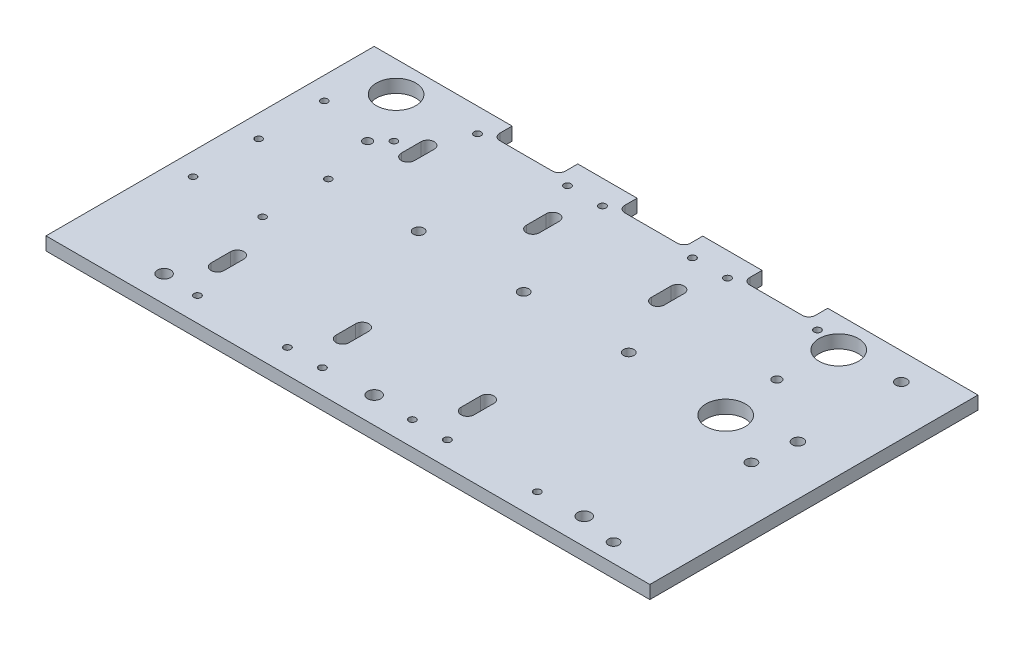
SolidWorks part; units mm, degrees
ref_plane "Front Plane" through (0, 0, 0) normal (0, 0, 1) x (1, 0, 0)
ref_plane "Top Plane" through (0, 0, 0) normal (0, 1, 0) x (1, 0, 0)
ref_plane "Right Plane" through (0, 0, 0) normal (1, 0, 0) x (0, 0, -1)
sketch "Sketch1" plane through (0, 0, 0) normal (0, 1, 0) x (1, 0, 0)
  line L1 (0, 0) -> (292.1, 0)
  line L2 (0, 0) -> (0, 158.75)
  line L3 (0, 158.75) -> (292.1, 158.75)
  line L4 (292.1, 0) -> (292.1, 158.75)
  dimension "D1" = 292.1
  dimension "D2" = 158.75
extrude "Boss-Extrude1" add sketch "Sketch1" along normal blind 6.35
sketch "Sketch2" plane through (0, 6.35, 0) normal (0, 1, 0) x (1, 0, 0)
  line L0 (0, 25.4) -> (292.1, 25.4) construction
  line L1 (0, 12.7) -> (292.1, 12.7) construction
  line L3 (146.05, 25.4) -> (146.05, 158.75) construction
  line L4 (0, 158.75) -> (0, 0)
  line L5 (0, 0) -> (292.1, 0)
  line L6 (292.1, 0) -> (292.1, 158.75)
  line L7 (292.1, 158.75) -> (0, 158.75)
  line L8 (0, 158.75) -> (0, 0) construction
  line L9 (0, 0) -> (292.1, 0) construction
  line L10 (292.1, 0) -> (292.1, 158.75) construction
  line L11 (292.1, 158.75) -> (0, 158.75) construction
  line L12 (292.1, 92.075) -> (0, 92.075) construction
  circle A0 centre (146.05, 12.7) radius 3.175
  circle A1 centre (247.65, 12.7) radius 3.175
  circle A2 centre (44.45, 12.7) radius 3.175
  point P8 (146.05, 92.075)
  dimension "D6" = 6.35
  dimension "D7" = 6.35
  dimension "D8" = 6.35
  dimension "D2" = 25.4
  dimension "D3" = 12.7
  dimension "D4" = 101.6
  dimension "D5" = 101.6
  dimension "D1" = 0
extrude "Cut-Extrude2" cut sketch "Sketch2" against normal blind 6.35
ref_plane "Plane2" through (0, 0, -79.375) normal (0, 0, 1) x (1, 0, 0)
ref_plane "Plane3" through (146.05, 0, 0) normal (-1, 0, 0) x (0, 0, 1)
ref_plane "Plane4" through (0, 0, -92.075) normal (0, 0, -1) x (-1, 0, 0)
sketch "Sketch4" plane through (0, 6.35, 0) normal (0, 1, 0) x (1, 0, 0)
  line L0 (92.964, 94.615) -> (83.439, 94.615) construction
  line L1 (83.439, 89.535) -> (92.964, 89.535) construction
  line L2 (143.764, 94.615) -> (134.239, 94.615) construction
  line L3 (134.239, 89.535) -> (143.764, 89.535) construction
  line L4 (194.564, 94.615) -> (185.039, 94.615) construction
  line L5 (185.039, 89.535) -> (194.564, 89.535) construction
  line L6 (270.764, 100.483) -> (270.764, 90.817) construction
  line L7 (265.43, 90.817) -> (265.43, 100.483) construction
  line L8 (265.43, 140.817) -> (265.43, 150.483) construction
  line L9 (270.764, 150.483) -> (270.764, 140.817) construction
  line L10 (211.4042, 52.4764) -> (218.4146, 52.4764)
  line L11 (211.4042, 74.4728) -> (211.4042, 52.4764)
  line L12 (292.1, 74.4728) -> (211.4042, 74.4728)
  line L13 (292.1, 52.4764) -> (292.1, 74.4728)
  line L14 (285.0896, 52.4764) -> (292.1, 52.4764)
  line L15 (292.1, 47.3964) -> (285.0896, 47.3964)
  line L16 (292.1, 25.4) -> (292.1, 47.3964)
  line L17 (211.4042, 25.4) -> (292.1, 25.4)
  line L18 (211.4042, 47.3964) -> (211.4042, 25.4)
  line L19 (218.4146, 47.3964) -> (211.4042, 47.3964)
  line L20 (211.4042, 52.4764) -> (218.4146, 52.4764) construction
  line L21 (211.4042, 74.4728) -> (211.4042, 52.4764) construction
  line L22 (292.1, 74.4728) -> (211.4042, 74.4728) construction
  line L23 (292.1, 52.4764) -> (292.1, 74.4728) construction
  line L24 (285.0896, 52.4764) -> (292.1, 52.4764) construction
  line L25 (292.1, 47.3964) -> (285.0896, 47.3964) construction
  line L26 (292.1, 25.4) -> (292.1, 47.3964) construction
  line L27 (211.4042, 25.4) -> (292.1, 25.4) construction
  line L28 (211.4042, 47.3964) -> (211.4042, 25.4) construction
  line L29 (218.4146, 47.3964) -> (211.4042, 47.3964) construction
  line L30 (92.964, 94.615) -> (83.439, 94.615) construction
  line L31 (83.439, 89.535) -> (92.964, 89.535) construction
  line L32 (143.764, 94.615) -> (134.239, 94.615) construction
  line L33 (134.239, 89.535) -> (143.764, 89.535) construction
  line L34 (194.564, 94.615) -> (185.039, 94.615) construction
  line L35 (185.039, 89.535) -> (194.564, 89.535) construction
  line L36 (270.764, 100.483) -> (270.764, 90.817) construction
  line L37 (265.43, 90.817) -> (265.43, 100.483) construction
  line L38 (265.43, 140.817) -> (265.43, 150.483) construction
  line L39 (270.764, 150.483) -> (270.764, 140.817) construction
  line L40 (194.564, 92.075) -> (185.039, 92.075) construction
  line L41 (185.039, 92.075) -> (143.764, 92.075) construction
  line L42 (143.764, 92.075) -> (134.239, 92.075) construction
  line L43 (134.239, 92.075) -> (92.964, 92.075) construction
  line L44 (92.964, 92.075) -> (83.439, 92.075) construction
  line L45 (268.097, 90.817) -> (268.097, 100.483) construction
  line L46 (268.097, 100.483) -> (268.097, 140.817) construction
  line L47 (268.097, 140.817) -> (268.097, 150.483) construction
  line L48 (107.6164, 149.625) -> (107.6164, 9.125) construction
  line L49 (107.6164, 9.125) -> (57.6164, 9.125) construction
  line L50 (57.6164, 9.125) -> (57.6164, 149.625) construction
  line L51 (57.6164, 149.625) -> (107.6164, 149.625) construction
  line L52 (228.5272, 9.125) -> (228.5272, 149.625)
  line L53 (178.5272, 9.125) -> (228.5272, 9.125)
  line L54 (178.5272, 149.625) -> (178.5272, 9.125)
  line L55 (228.5272, 149.625) -> (178.5272, 149.625)
  line L56 (228.5272, 9.125) -> (228.5272, 149.625) construction
  line L57 (178.5272, 9.125) -> (228.5272, 9.125) construction
  line L58 (178.5272, 149.625) -> (178.5272, 9.125) construction
  line L59 (228.5272, 149.625) -> (178.5272, 149.625) construction
  line L60 (168.0718, 149.625) -> (168.0718, 9.125) construction
  line L61 (168.0718, 9.125) -> (118.0718, 9.125) construction
  line L62 (118.0718, 9.125) -> (118.0718, 149.625) construction
  line L63 (118.0718, 149.625) -> (168.0718, 149.625) construction
  line L64 (107.6164, 149.625) -> (107.6164, 9.125) construction
  line L65 (107.6164, 9.125) -> (57.6164, 9.125) construction
  line L66 (57.6164, 9.125) -> (57.6164, 149.625) construction
  line L67 (57.6164, 149.625) -> (107.6164, 149.625) construction
  line L68 (168.0718, 149.625) -> (168.0718, 9.125) construction
  line L69 (168.0718, 9.125) -> (118.0718, 9.125) construction
  line L70 (118.0718, 9.125) -> (118.0718, 149.625) construction
  line L71 (118.0718, 149.625) -> (168.0718, 149.625) construction
  line L72 (114.8968, 130.175) -> (114.8968, 120.65) construction
  line L73 (118.0718, 130.175) -> (118.0718, 120.65)
  line L74 (111.7218, 130.175) -> (111.7218, 120.65)
  line L75 (54.4414, 130.175) -> (54.4414, 120.65) construction
  line L76 (57.6164, 130.175) -> (57.6164, 120.65)
  line L77 (51.2664, 130.175) -> (51.2664, 120.65)
  line L78 (175.3522, 130.175) -> (175.3522, 120.65) construction
  line L79 (178.5272, 130.175) -> (178.5272, 120.65)
  line L80 (172.1772, 130.175) -> (172.1772, 120.65)
  line L81 (114.8968, 130.175) -> (175.3522, 130.175) construction
  line L82 (175.3522, 38.1) -> (175.3522, 28.575) construction
  line L83 (178.5272, 38.1) -> (178.5272, 28.575)
  line L84 (172.1772, 38.1) -> (172.1772, 28.575)
  line L85 (54.4414, 38.1) -> (54.4414, 28.575) construction
  line L86 (57.6164, 38.1) -> (57.6164, 28.575)
  line L87 (51.2664, 38.1) -> (51.2664, 28.575)
  line L88 (114.8968, 38.1) -> (114.8968, 28.575) construction
  line L89 (118.0718, 38.1) -> (118.0718, 28.575)
  line L90 (111.7218, 38.1) -> (111.7218, 28.575)
  line L91 (114.8968, 28.575) -> (54.4414, 28.575) construction
  line L92 (54.4414, 28.575) -> (87.842, 28.575) construction
  line L93 (114.8968, 120.65) -> (114.8968, 38.1) construction
  line L94 (54.4414, 120.65) -> (54.4414, 38.1) construction
  line L95 (175.3522, 120.65) -> (175.3522, 69.0871) construction
  line L96 (292.1, 25.4) -> (0, 25.4) construction
  line L97 (292.1, 25.4) -> (0, 25.4) construction
  line L98 (95.3164, 152.8) -> (69.9164, 152.8) construction
  line L99 (95.3164, 149.625) -> (69.9164, 149.625)
  line L100 (76.2, 117.475) -> (215.9, 117.475) construction
  line L101 (127.1968, 152.8) -> (127.1968, 158.75)
  line L102 (158.9468, 152.8) -> (158.9468, 158.75)
  line L103 (13.9574, 117.475) -> (215.9, 117.475) construction
  line L104 (98.4914, 158.75) -> (66.7414, 158.75)
  line L105 (158.9468, 158.75) -> (127.1968, 158.75)
  line L106 (219.4022, 158.75) -> (187.6522, 158.75)
  line L107 (82.6164, 149.625) -> (82.6164, 158.75) construction
  line L108 (143.0718, 149.625) -> (143.0718, 158.75) construction
  line L109 (203.5272, 149.625) -> (203.5272, 158.75) construction
  line L110 (143.0718, 149.625) -> (143.0718, 158.75) construction
  line L111 (155.7718, 152.8) -> (130.3718, 152.8) construction
  line L112 (66.7414, 152.8) -> (66.7414, 158.75)
  line L113 (98.4914, 152.8) -> (98.4914, 158.75)
  line L114 (203.5272, 149.625) -> (203.5272, 158.75) construction
  line L115 (25.4, 143.962) -> (25.4, 158.75) construction
  line L116 (25.4, 143.962) -> (0, 143.962) construction
  line L117 (0, 158.75) -> (0, 0) construction
  line L118 (0, 133.35) -> (292.1, 133.35) construction
  line L119 (0, 158.75) -> (0, 0) construction
  line L120 (292.1, 0) -> (292.1, 158.75) construction
  line L121 (292.1, 158.75) -> (0, 158.75) construction
  line L122 (252.222, 85.725) -> (252.222, 155.575) construction
  line L123 (252.222, 85.725) -> (252.222, 155.575) construction
  line L124 (239.522, 116.6114) -> (234.8772, 116.6114) construction
  line L125 (143.0718, 149.625) -> (143.0718, 158.75) construction
  line L127 (155.7718, 149.625) -> (130.3718, 149.625)
  line L129 (203.5272, 149.625) -> (203.5272, 158.75) construction
  line L130 (187.6522, 152.8) -> (187.6522, 158.75)
  line L131 (216.2272, 152.8) -> (190.8272, 152.8) construction
  line L132 (219.4022, 152.8) -> (219.4022, 158.75)
  line L133 (216.2272, 149.625) -> (190.8272, 149.625)
  line L144 (175.3522, 69.0871) -> (175.3522, 3.6827) construction
  line L173 (234.8772, 149.625) -> (234.8772, 9.125) construction
  line L194 (239.522, 143.962) -> (239.522, 89.2608) construction
  line L195 (25.4, 143.962) -> (239.522, 143.962) construction
  circle A0 centre (88.2015, 92.075) radius 2.54
  arc A1 (92.964, 89.535) -> (92.964, 94.615) centre (92.964, 92.075) ccw construction
  arc A2 (83.439, 94.615) -> (83.439, 89.535) centre (83.439, 92.075) ccw construction
  arc A3 (285.0896, 52.4764) -> (285.0896, 47.3964) centre (285.0896, 49.9364) ccw
  arc A4 (218.4146, 47.3964) -> (218.4146, 52.4764) centre (218.4146, 49.9364) ccw
  arc A5 (285.0896, 52.4764) -> (285.0896, 47.3964) centre (285.0896, 49.9364) ccw construction
  arc A6 (218.4146, 47.3964) -> (218.4146, 52.4764) centre (218.4146, 49.9364) ccw construction
  arc A7 (134.239, 94.615) -> (134.239, 89.535) centre (134.239, 92.075) ccw construction
  arc A8 (143.764, 89.535) -> (143.764, 94.615) centre (143.764, 92.075) ccw construction
  arc A9 (185.039, 94.615) -> (185.039, 89.535) centre (185.039, 92.075) ccw construction
  arc A10 (194.564, 89.535) -> (194.564, 94.615) centre (194.564, 92.075) ccw construction
  arc A11 (265.43, 90.817) -> (270.764, 90.817) centre (268.097, 90.817) ccw construction
  arc A12 (270.764, 100.483) -> (265.43, 100.483) centre (268.097, 100.483) ccw construction
  arc A13 (265.43, 140.817) -> (270.764, 140.817) centre (268.097, 140.817) ccw construction
  arc A14 (270.764, 150.483) -> (265.43, 150.483) centre (268.097, 150.483) ccw construction
  arc A15 (92.964, 89.535) -> (92.964, 94.615) centre (92.964, 92.075) ccw construction
  arc A16 (83.439, 94.615) -> (83.439, 89.535) centre (83.439, 92.075) ccw construction
  arc A17 (134.239, 94.615) -> (134.239, 89.535) centre (134.239, 92.075) ccw construction
  arc A18 (143.764, 89.535) -> (143.764, 94.615) centre (143.764, 92.075) ccw construction
  arc A19 (185.039, 94.615) -> (185.039, 89.535) centre (185.039, 92.075) ccw construction
  arc A20 (194.564, 89.535) -> (194.564, 94.615) centre (194.564, 92.075) ccw construction
  arc A21 (265.43, 90.817) -> (270.764, 90.817) centre (268.097, 90.817) ccw construction
  arc A22 (270.764, 100.483) -> (265.43, 100.483) centre (268.097, 100.483) ccw construction
  arc A23 (265.43, 140.817) -> (270.764, 140.817) centre (268.097, 140.817) ccw construction
  arc A24 (270.764, 150.483) -> (265.43, 150.483) centre (268.097, 150.483) ccw construction
  circle A25 centre (44.45, 123.825) radius 1.651 construction
  circle A26 centre (44.45, 92.075) radius 1.651 construction
  circle A27 centre (44.45, 60.325) radius 1.651 construction
  circle A28 centre (10.795, 123.825) radius 1.651 construction
  circle A29 centre (10.795, 92.075) radius 1.651 construction
  circle A30 centre (10.795, 60.325) radius 1.651 construction
  circle A31 centre (44.45, 123.825) radius 1.651
  circle A32 centre (44.45, 92.075) radius 1.651
  circle A33 centre (44.45, 60.325) radius 1.651
  circle A34 centre (10.795, 123.825) radius 1.651
  circle A35 centre (10.795, 92.075) radius 1.651
  circle A36 centre (10.795, 60.325) radius 1.651
  circle A37 centre (139.0015, 92.075) radius 2.54
  circle A38 centre (189.8015, 92.075) radius 2.54
  arc A39 (263.0236, 75.6854) -> (268.1036, 75.6854) centre (265.5636, 75.6854) ccw construction
  arc A40 (268.1036, 9.0104) -> (263.0236, 9.0104) centre (265.5636, 9.0104) ccw construction
  circle A41 centre (268.097, 145.65) radius 2.667
  circle A42 centre (268.097, 95.65) radius 2.667
  arc A43 (118.0718, 130.175) -> (111.7218, 130.175) centre (114.8968, 130.175) ccw
  arc A44 (111.7218, 120.65) -> (118.0718, 120.65) centre (114.8968, 120.65) ccw
  arc A45 (57.6164, 130.175) -> (51.2664, 130.175) centre (54.4414, 130.175) ccw
  arc A46 (51.2664, 120.65) -> (57.6164, 120.65) centre (54.4414, 120.65) ccw
  arc A47 (178.5272, 130.175) -> (172.1772, 130.175) centre (175.3522, 130.175) ccw
  arc A48 (172.1772, 120.65) -> (178.5272, 120.65) centre (175.3522, 120.65) ccw
  arc A49 (178.5272, 38.1) -> (172.1772, 38.1) centre (175.3522, 38.1) ccw
  arc A50 (172.1772, 28.575) -> (178.5272, 28.575) centre (175.3522, 28.575) ccw
  arc A51 (57.6164, 38.1) -> (51.2664, 38.1) centre (54.4414, 38.1) ccw
  arc A52 (51.2664, 28.575) -> (57.6164, 28.575) centre (54.4414, 28.575) ccw
  arc A53 (118.0718, 38.1) -> (111.7218, 38.1) centre (114.8968, 38.1) ccw
  arc A54 (111.7218, 28.575) -> (118.0718, 28.575) centre (114.8968, 28.575) ccw
  arc A55 (98.4914, 152.8) -> (95.3164, 149.625) centre (95.3164, 152.8) cw
  arc A56 (66.7414, 152.8) -> (69.9164, 149.625) centre (69.9164, 152.8) ccw
  circle A57 centre (226.0272, 147.125) radius 1.7 construction
  circle A58 centre (182.5272, 147.125) radius 1.7 construction
  circle A59 centre (165.5718, 147.125) radius 1.7 construction
  circle A60 centre (122.0718, 147.125) radius 1.7 construction
  arc A61 (158.9468, 152.8) -> (155.7718, 149.625) centre (155.7718, 152.8) cw
  arc A62 (127.1968, 152.8) -> (130.3718, 149.625) centre (130.3718, 152.8) ccw
  arc A63 (219.4022, 152.8) -> (216.2272, 149.625) centre (216.2272, 152.8) cw
  arc A64 (187.6522, 152.8) -> (190.8272, 149.625) centre (190.8272, 152.8) ccw
  circle A65 centre (105.1164, 147.125) radius 1.7 construction
  circle A66 centre (61.6164, 147.125) radius 1.7 construction
  circle A67 centre (182.5272, 11.625) radius 1.7 construction
  circle A68 centre (226.0272, 11.625) radius 1.7 construction
  circle A69 centre (165.5718, 11.625) radius 1.7 construction
  circle A70 centre (122.0718, 11.625) radius 1.7 construction
  circle A71 centre (105.1164, 11.625) radius 1.7 construction
  circle A72 centre (61.6164, 11.625) radius 1.7 construction
  circle A73 centre (226.0272, 147.125) radius 1.7
  circle A74 centre (182.5272, 147.125) radius 1.7
  circle A75 centre (165.5718, 147.125) radius 1.7
  circle A76 centre (122.0718, 147.125) radius 1.7
  circle A77 centre (105.1164, 147.125) radius 1.7
  circle A78 centre (61.6164, 147.125) radius 1.7
  circle A79 centre (182.5272, 11.625) radius 1.7
  circle A80 centre (226.0272, 11.625) radius 1.7
  circle A81 centre (165.5718, 11.625) radius 1.7
  circle A82 centre (122.0718, 11.625) radius 1.7
  circle A83 centre (105.1164, 11.625) radius 1.7
  circle A84 centre (61.6164, 11.625) radius 1.7
  circle A85 centre (62.1164, 71.125) radius 1.7 construction
  circle A86 centre (62.1164, 82.625) radius 1.7 construction
  circle A87 centre (62.1164, 26.125) radius 1.7 construction
  circle A88 centre (62.1164, 35.625) radius 1.7 construction
  circle A89 centre (62.1164, 45.125) radius 1.7 construction
  circle A90 centre (62.1164, 104.625) radius 1.7 construction
  circle A91 centre (62.1164, 114.125) radius 1.7 construction
  circle A92 centre (62.1164, 123.625) radius 1.7 construction
  circle A93 centre (236.9727, 116.6114) radius 2.0955 construction
  circle A94 centre (236.9727, 116.6114) radius 2.0955
  circle A95 centre (62.1164, 71.125) radius 1.7 construction
  circle A96 centre (62.1164, 82.625) radius 1.7 construction
  circle A97 centre (62.1164, 26.125) radius 1.7 construction
  circle A98 centre (62.1164, 35.625) radius 1.7 construction
  circle A99 centre (239.522, 89.2608) radius 9.525
  circle A100 centre (239.522, 143.962) radius 9.525
  circle A101 centre (25.4, 143.962) radius 9.525
  circle A102 centre (62.1164, 45.125) radius 1.7 construction
  circle A103 centre (62.1164, 104.625) radius 1.7 construction
  circle A104 centre (62.1164, 114.125) radius 1.7 construction
  circle A105 centre (62.1164, 123.625) radius 1.7 construction
  arc A106 (263.0236, 75.6854) -> (268.1036, 75.6854) centre (265.5636, 75.6854) ccw construction
  arc A107 (268.1036, 9.0104) -> (263.0236, 9.0104) centre (265.5636, 9.0104) ccw construction
  circle A108 centre (265.5636, 75.6854) radius 2.54
  circle A109 centre (265.5636, 9.0104) radius 2.54
  circle A110 centre (38.1, 117.475) radius 2.0955
  point P100 (114.8968, 125.4125)
  point P105 (54.4414, 125.4125)
  point P112 (175.3522, 125.4125)
  point P121 (175.3522, 33.3375)
  point P128 (54.4414, 33.3375)
  point P135 (114.8968, 33.3375)
  point P142 (114.8968, 25.4)
  point P152 (82.6164, 152.8)
  point P159 (143.0718, 152.8)
  point P211 (203.5272, 152.8)
  dimension "D1" = 0
  dimension "D3" = 3.175
  dimension "D5" = 3.175
  dimension "D8" = 3.175
  dimension "D10" = 3.175
  dimension "D12" = 19.05
  dimension "D4" = 25.4
  dimension "D7" = 25.4
  dimension "D6" = 25.4
  dimension "D9" = 25.4
  dimension "D11" = 6.35
  dimension "D13" = 14.788
  dimension "D14" = 25.4
  dimension "D16" = 38.1
  dimension "D15" = 14.788
  dimension "D17" = 25.4
extrude "Cut-Extrude5" cut sketch "Sketch4" against normal through all
equation "\"D5@Sketch2\"=\"D4@Sketch2\""
equation "\"D7@Sketch2\"=\"D6@Sketch2\""
equation "\"D8@Sketch2\"=\"D7@Sketch2\""
equation "\"D13@Sketch4\"=\"D15@Sketch4\""
